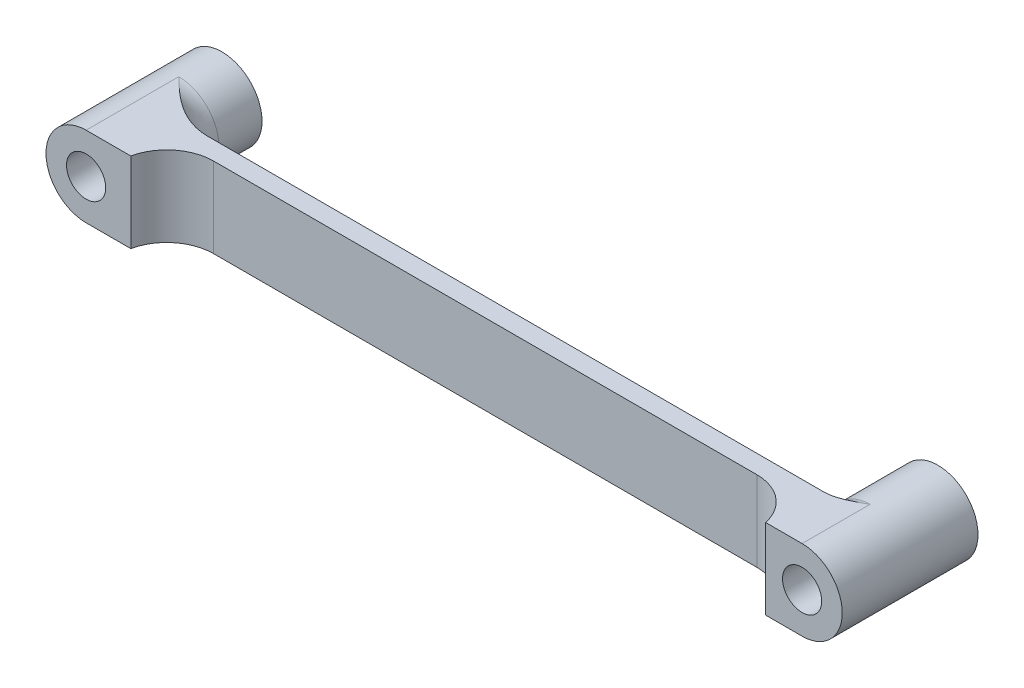
SolidWorks part; units mm, degrees
ref_plane "Front Plane" through (0, 0, 0) normal (0, 0, 1) x (1, 0, 0)
ref_plane "Top Plane" through (0, 0, 0) normal (0, 1, 0) x (1, 0, 0)
ref_plane "Right Plane" through (0, 0, 0) normal (1, 0, 0) x (0, 0, -1)
sketch "Sketch1" plane through (0, 0, 0) normal (0, 0, 1) x (1, 0, 0)
  circle A0 centre (19, -24.5) radius 1.5875
  circle A1 centre (19, -24.5) radius 3.25 construction
  circle A2 centre (19, -24.5) radius 3.25
  circle A3 centre (-39, -24.5) radius 3.25 construction
  circle A4 centre (-39, -24.5) radius 3.25
  circle A5 centre (-39, -24.5) radius 1.5875
  dimension "D1" = 3.175
extrude "Boss-Extrude1" add sketch "Sketch1" along normal blind 6.5
sketch "Sketch2" plane through (0, 0, 6.5) normal (0, 0, 1) x (1, 0, 0)
  line L0 (19, -24.5) -> (-39, -24.5) construction
  line L1 (19, -27.75) -> (-39, -27.75)
  line L2 (19, -21.25) -> (-39, -21.25)
  arc A0 (19, -27.75) -> (19, -21.25) centre (19, -24.5) ccw
  arc A1 (-39, -21.25) -> (-39, -27.75) centre (-39, -24.5) ccw
  circle A2 centre (-39, -24.5) radius 3.25 construction
  circle A3 centre (-39, -24.5) radius 1.5875 construction
  circle A4 centre (19, -24.5) radius 1.5875 construction
  circle A5 centre (-39, -24.5) radius 1.5875
  circle A6 centre (19, -24.5) radius 1.5875
  point P4 (-10, -24.5)
extrude "Boss-Extrude2" add sketch "Sketch2" along normal blind 4.5
fillet "Fillet1" radius 3 1 edges at (-35.75, -24.5, 6.5)
fillet "Fillet2" radius 1 1 edges at (15.75, -24.5, 6.5)
sketch "Sketch3" plane through (0, -27.75, 0) normal (0, -1, 0) x (1, 0, 0)
  line L0 (-31.6697, 11.8) -> (12.3303, 11.8) construction
  line L1 (-31.6697, 15.6) -> (12.3303, 15.6)
  line L2 (-31.6697, 8) -> (12.3303, 8)
  arc A0 (-31.6697, 15.6) -> (-31.6697, 8) centre (-31.6697, 11.8) ccw
  arc A1 (12.3303, 8) -> (12.3303, 15.6) centre (12.3303, 11.8) ccw
  point P4 (-9.6697, 11.8)
  dimension "D1" = 3.8
extrude "Cut-Extrude1" cut sketch "Sketch3" against normal through all
